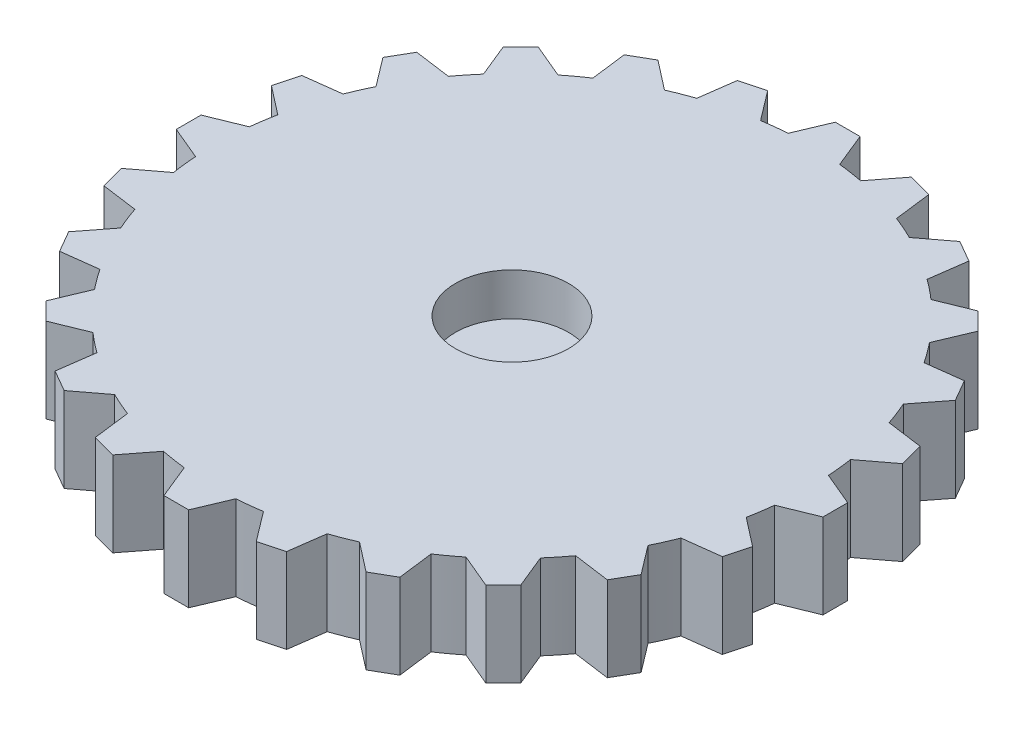
SolidWorks part; units mm, degrees
ref_plane "Front Plane" through (0, 0, 0) normal (0, 0, 1) x (1, 0, 0)
ref_plane "Top Plane" through (0, 0, 0) normal (0, 1, 0) x (1, 0, 0)
ref_plane "Right Plane" through (0, 0, 0) normal (1, 0, 0) x (0, 0, -1)
sketch "Sketch1" plane through (0, 0, 0) normal (0, 1, 0) x (1, 0, 0)
  line L111 (-0.5, 14.7462) -> (0.5, 14.7462)
  line L112 (0.5, 14.7462) -> (2, 12.5441)
  line L113 (-0.5, 14.7462) -> (-2, 12.5441)
  line L114 (6.433, 12.8885) -> (6.631, 10.2315)
  line L115 (5.567, 13.3885) -> (6.433, 12.8885)
  line L116 (5.567, 13.3885) -> (3.1669, 12.2315)
  line L117 (10.6423, 8.3132) -> (9.4853, 5.9131)
  line L118 (10.1423, 9.1792) -> (10.6423, 8.3132)
  line L119 (10.1423, 9.1792) -> (7.4853, 9.3772)
  line L120 (12, 2.2462) -> (9.798, 0.7462)
  line L121 (12, 3.2462) -> (12, 2.2462)
  line L122 (12, 3.2462) -> (9.798, 4.7462)
  line L123 (10.1423, -3.6868) -> (7.4853, -3.8849)
  line L124 (10.6423, -2.8208) -> (10.1423, -3.6868)
  line L125 (10.6423, -2.8208) -> (9.4853, -0.4208)
  line L126 (5.567, -7.8961) -> (3.1669, -6.7391)
  line L127 (6.433, -7.3961) -> (5.567, -7.8961)
  line L128 (6.433, -7.3961) -> (6.631, -4.7391)
  line L129 (-0.5, -9.2538) -> (-2, -7.0518)
  line L130 (0.5, -9.2538) -> (-0.5, -9.2538)
  line L131 (0.5, -9.2538) -> (2, -7.0518)
  line L132 (-6.433, -7.3961) -> (-6.631, -4.7391)
  line L133 (-5.567, -7.8961) -> (-6.433, -7.3961)
  line L134 (-5.567, -7.8961) -> (-3.1669, -6.7391)
  line L135 (-10.6423, -2.8208) -> (-9.4853, -0.4208)
  line L136 (-10.1423, -3.6868) -> (-10.6423, -2.8208)
  line L137 (-10.1423, -3.6868) -> (-7.4853, -3.8849)
  line L138 (-12, 3.2462) -> (-9.798, 4.7462)
  line L139 (-12, 2.2462) -> (-12, 3.2462)
  line L140 (-12, 2.2462) -> (-9.798, 0.7462)
  line L141 (-10.1423, 9.1792) -> (-7.4853, 9.3772)
  line L142 (-10.6423, 8.3132) -> (-10.1423, 9.1792)
  line L143 (-10.6423, 8.3132) -> (-9.4853, 5.9131)
  line L144 (-5.567, 13.3885) -> (-3.1669, 12.2315)
  line L145 (-6.433, 12.8885) -> (-5.567, 13.3885)
  line L146 (-6.433, 12.8885) -> (-6.631, 10.2315)
  arc A43 (-2, 12.5441) -> (-3.1669, 12.2315) centre (0, 2.7462) ccw
  arc A44 (-6.631, 10.2315) -> (-7.4853, 9.3772) centre (0, 2.7462) ccw
  arc A45 (-9.4853, 5.9131) -> (-9.798, 4.7462) centre (0, 2.7462) ccw
  arc A46 (-9.798, 0.7462) -> (-9.4853, -0.4208) centre (0, 2.7462) ccw
  arc A47 (-7.4853, -3.8849) -> (-6.631, -4.7391) centre (0, 2.7462) ccw
  arc A48 (-3.1669, -6.7391) -> (-2, -7.0518) centre (0, 2.7462) ccw
  arc A49 (2, -7.0518) -> (3.1669, -6.7391) centre (0, 2.7462) ccw
  arc A50 (6.631, -4.7391) -> (7.4853, -3.8849) centre (0, 2.7462) ccw
  arc A51 (9.4853, -0.4208) -> (9.798, 0.7462) centre (0, 2.7462) ccw
  arc A52 (9.798, 4.7462) -> (9.4853, 5.9131) centre (0, 2.7462) ccw
  arc A53 (7.4853, 9.3772) -> (6.631, 10.2315) centre (0, 2.7462) ccw
  arc A54 (3.1669, 12.2315) -> (2, 12.5441) centre (0, 2.7462) ccw
  point P6 (0, 0)
  point P8 (0, 0)
  point P9 (0, 0)
  point P12 (0, 2.7462)
  point P17 (0, 0)
  point P18 (0, 2.7462)
  point P22 (-2.5, 0.7462)
  point P63 (0, 0)
  point P68 (0, 0)
  point P69 (0, 2.7462)
  point P119 (0, 0)
  dimension "D1" = 20
  dimension "D8" = 12
sketch "Sketch2" plane through (0, 0, 0) normal (0, 1, 0) x (1, 0, 0)
  line L0 (-2, 0) -> (2, 0)
  line L1 (-23, -0.1) -> (-23, 0.1)
  line L2 (-21.1, 2) -> (-19.8997, 2)
  line L3 (-21.1, -2) -> (-19.8997, -2)
  line L4 (-20.6853, 4.6181) -> (-19.5438, 4.2472)
  line L5 (-19.4493, 8.4224) -> (-18.3078, 8.0515)
  line L6 (-21.9052, 7.0123) -> (-21.8434, 7.2025)
  line L7 (-18.2458, 10.7842) -> (-17.2748, 10.0787)
  line L8 (-15.8947, 14.0203) -> (-14.9237, 13.3148)
  line L9 (-18.6662, 13.4382) -> (-18.5486, 13.6)
  line L10 (-14.0203, 15.8947) -> (-13.3148, 14.9237)
  line L11 (-10.7842, 18.2458) -> (-10.0787, 17.2748)
  line L12 (-13.6, 18.5486) -> (-13.4382, 18.6662)
  line L13 (-8.4224, 19.4493) -> (-8.0515, 18.3078)
  line L14 (-4.6181, 20.6853) -> (-4.2472, 19.5438)
  line L15 (-7.2025, 21.8434) -> (-7.0123, 21.9052)
  line L16 (-2, 21.1) -> (-2, 19.8997)
  line L17 (2, 21.1) -> (2, 19.8997)
  line L18 (-0.1, 23) -> (0.1, 23)
  line L19 (4.6181, 20.6853) -> (4.2472, 19.5438)
  line L20 (8.4224, 19.4493) -> (8.0515, 18.3078)
  line L21 (7.0123, 21.9052) -> (7.2025, 21.8434)
  line L22 (10.7842, 18.2458) -> (10.0787, 17.2748)
  line L23 (14.0203, 15.8947) -> (13.3148, 14.9237)
  line L24 (13.4382, 18.6662) -> (13.6, 18.5486)
  line L25 (15.8947, 14.0203) -> (14.9237, 13.3148)
  line L26 (18.2458, 10.7842) -> (17.2748, 10.0787)
  line L27 (18.5486, 13.6) -> (18.6662, 13.4382)
  line L28 (19.4493, 8.4224) -> (18.3078, 8.0515)
  line L29 (20.6853, 4.6181) -> (19.5438, 4.2472)
  line L30 (21.8434, 7.2025) -> (21.9052, 7.0123)
  line L31 (21.1, 2) -> (19.8997, 2)
  line L32 (21.1, -2) -> (19.8997, -2)
  line L33 (23, 0.1) -> (23, -0.1)
  line L34 (20.6853, -4.6181) -> (19.5438, -4.2472)
  line L35 (19.4493, -8.4224) -> (18.3078, -8.0515)
  line L36 (21.9052, -7.0123) -> (21.8434, -7.2025)
  line L37 (18.2458, -10.7842) -> (17.2748, -10.0787)
  line L38 (15.8947, -14.0203) -> (14.9237, -13.3148)
  line L39 (18.6662, -13.4382) -> (18.5486, -13.6)
  line L40 (14.0203, -15.8947) -> (13.3148, -14.9237)
  line L41 (10.7842, -18.2458) -> (10.0787, -17.2748)
  line L42 (13.6, -18.5486) -> (13.4382, -18.6662)
  line L43 (8.4224, -19.4493) -> (8.0515, -18.3078)
  line L44 (4.6181, -20.6853) -> (4.2472, -19.5438)
  line L45 (7.2025, -21.8434) -> (7.0123, -21.9052)
  line L46 (2, -21.1) -> (2, -19.8997)
  line L47 (-2, -21.1) -> (-2, -19.8997)
  line L48 (0.1, -23) -> (-0.1, -23)
  line L49 (-4.6181, -20.6853) -> (-4.2472, -19.5438)
  line L50 (-8.4224, -19.4493) -> (-8.0515, -18.3078)
  line L51 (-7.0123, -21.9052) -> (-7.2025, -21.8434)
  line L52 (-10.7842, -18.2458) -> (-10.0787, -17.2748)
  line L53 (-14.0203, -15.8947) -> (-13.3148, -14.9237)
  line L54 (-13.4382, -18.6662) -> (-13.6, -18.5486)
  line L55 (-15.8947, -14.0203) -> (-14.9237, -13.3148)
  line L56 (-18.2458, -10.7842) -> (-17.2748, -10.0787)
  line L57 (-18.5486, -13.6) -> (-18.6662, -13.4382)
  line L58 (-19.4493, -8.4224) -> (-18.3078, -8.0515)
  line L59 (-20.6853, -4.6181) -> (-19.5438, -4.2472)
  line L60 (-21.8434, -7.2025) -> (-21.9052, -7.0123)
  arc A0 (-18.3078, -8.0515) -> (-17.2748, -10.0787) centre (0, 0) ccw
  arc A1 (-21.1, 2) -> (-23, 0.1) centre (-21.1, 0.1) ccw
  arc A2 (-21.1, -2) -> (-23, -0.1) centre (-21.1, -0.1) cw
  arc A3 (-20.6853, 4.6181) -> (-21.9052, 7.0123) centre (-20.0982, 6.4252) cw
  arc A4 (-19.4493, 8.4224) -> (-21.8434, 7.2025) centre (-20.0364, 6.6154) ccw
  arc A5 (-18.2458, 10.7842) -> (-18.6662, 13.4382) centre (-17.129, 12.3214) cw
  arc A6 (-15.8947, 14.0203) -> (-18.5486, 13.6) centre (-17.0115, 12.4832) ccw
  arc A7 (-14.0203, 15.8947) -> (-13.6, 18.5486) centre (-12.4832, 17.0115) cw
  arc A8 (-10.7842, 18.2458) -> (-13.4382, 18.6662) centre (-12.3214, 17.129) ccw
  arc A9 (-8.4224, 19.4493) -> (-7.2025, 21.8434) centre (-6.6154, 20.0364) cw
  arc A10 (-4.6181, 20.6853) -> (-7.0123, 21.9052) centre (-6.4252, 20.0982) ccw
  arc A11 (-2, 21.1) -> (-0.1, 23) centre (-0.1, 21.1) cw
  arc A12 (2, 21.1) -> (0.1, 23) centre (0.1, 21.1) ccw
  arc A13 (4.6181, 20.6853) -> (7.0123, 21.9052) centre (6.4252, 20.0982) cw
  arc A14 (8.4224, 19.4493) -> (7.2025, 21.8434) centre (6.6154, 20.0364) ccw
  arc A15 (10.7842, 18.2458) -> (13.4382, 18.6662) centre (12.3214, 17.129) cw
  arc A16 (14.0203, 15.8947) -> (13.6, 18.5486) centre (12.4832, 17.0115) ccw
  arc A17 (15.8947, 14.0203) -> (18.5486, 13.6) centre (17.0115, 12.4832) cw
  arc A18 (18.2458, 10.7842) -> (18.6662, 13.4382) centre (17.129, 12.3214) ccw
  arc A19 (19.4493, 8.4224) -> (21.8434, 7.2025) centre (20.0364, 6.6154) cw
  arc A20 (20.6853, 4.6181) -> (21.9052, 7.0123) centre (20.0982, 6.4252) ccw
  arc A21 (21.1, 2) -> (23, 0.1) centre (21.1, 0.1) cw
  arc A22 (21.1, -2) -> (23, -0.1) centre (21.1, -0.1) ccw
  arc A23 (20.6853, -4.6181) -> (21.9052, -7.0123) centre (20.0982, -6.4252) cw
  arc A24 (19.4493, -8.4224) -> (21.8434, -7.2025) centre (20.0364, -6.6154) ccw
  arc A25 (18.2458, -10.7842) -> (18.6662, -13.4382) centre (17.129, -12.3214) cw
  arc A26 (15.8947, -14.0203) -> (18.5486, -13.6) centre (17.0115, -12.4832) ccw
  arc A27 (14.0203, -15.8947) -> (13.6, -18.5486) centre (12.4832, -17.0115) cw
  arc A28 (10.7842, -18.2458) -> (13.4382, -18.6662) centre (12.3214, -17.129) ccw
  arc A29 (8.4224, -19.4493) -> (7.2025, -21.8434) centre (6.6154, -20.0364) cw
  arc A30 (4.6181, -20.6853) -> (7.0123, -21.9052) centre (6.4252, -20.0982) ccw
  arc A31 (2, -21.1) -> (0.1, -23) centre (0.1, -21.1) cw
  arc A32 (-2, -21.1) -> (-0.1, -23) centre (-0.1, -21.1) ccw
  arc A33 (-4.6181, -20.6853) -> (-7.0123, -21.9052) centre (-6.4252, -20.0982) cw
  arc A34 (-8.4224, -19.4493) -> (-7.2025, -21.8434) centre (-6.6154, -20.0364) ccw
  arc A35 (-10.7842, -18.2458) -> (-13.4382, -18.6662) centre (-12.3214, -17.129) cw
  arc A36 (-14.0203, -15.8947) -> (-13.6, -18.5486) centre (-12.4832, -17.0115) ccw
  arc A37 (-15.8947, -14.0203) -> (-18.5486, -13.6) centre (-17.0115, -12.4832) cw
  arc A38 (-18.2458, -10.7842) -> (-18.6662, -13.4382) centre (-17.129, -12.3214) ccw
  arc A39 (-19.4493, -8.4224) -> (-21.8434, -7.2025) centre (-20.0364, -6.6154) cw
  arc A40 (-20.6853, -4.6181) -> (-21.9052, -7.0123) centre (-20.0982, -6.4252) ccw
  arc A41 (-19.8997, -2) -> (-19.5438, -4.2472) centre (0, 0) ccw
  arc A42 (-19.5438, 4.2472) -> (-19.8997, 2) centre (0, 0) ccw
  arc A43 (-17.2748, 10.0787) -> (-18.3078, 8.0515) centre (0, 0) ccw
  arc A44 (-13.3148, 14.9237) -> (-14.9237, 13.3148) centre (0, 0) ccw
  arc A45 (-8.0515, 18.3078) -> (-10.0787, 17.2748) centre (0, 0) ccw
  arc A46 (-2, 19.8997) -> (-4.2472, 19.5438) centre (0, 0) ccw
  arc A47 (4.2472, 19.5438) -> (2, 19.8997) centre (0, 0) ccw
  arc A48 (10.0787, 17.2748) -> (8.0515, 18.3078) centre (0, 0) ccw
  arc A49 (14.9237, 13.3148) -> (13.3148, 14.9237) centre (0, 0) ccw
  arc A50 (18.3078, 8.0515) -> (17.2748, 10.0787) centre (0, 0) ccw
  arc A51 (19.8997, 2) -> (19.5438, 4.2472) centre (0, 0) ccw
  arc A52 (19.5438, -4.2472) -> (19.8997, -2) centre (0, 0) ccw
  arc A53 (17.2748, -10.0787) -> (18.3078, -8.0515) centre (0, 0) ccw
  arc A54 (13.3148, -14.9237) -> (14.9237, -13.3148) centre (0, 0) ccw
  arc A55 (8.0515, -18.3078) -> (10.0787, -17.2748) centre (0, 0) ccw
  arc A56 (2, -19.8997) -> (4.2472, -19.5438) centre (0, 0) ccw
  arc A57 (-10.0787, -17.2748) -> (-8.0515, -18.3078) centre (0, 0) ccw
  arc A58 (-4.2472, -19.5438) -> (-2, -19.8997) centre (0, 0) ccw
  arc A59 (-14.9237, -13.3148) -> (-13.3148, -14.9237) centre (0, 0) ccw
  point P6 (0, 0)
  point P10 (-23, 2)
  point P170 (0, 0)
  dimension "D1" = 40
  dimension "D4" = 1.9
  dimension "D5" = 20
sketch "Sketch3" plane through (0, 0, 0) normal (0, 1, 0) x (1, 0, 0)
  line L0 (20.6069, -4.0443) -> (20.351, -4.9991) construction
  line L1 (23.3015, -1.3115) -> (23.3015, 0.4385)
  line L2 (23.3015, 0.4385) -> (20.9515, 1.4269)
  line L3 (23.3015, -1.3115) -> (20.8737, -2.3)
  line L4 (22.621, -5.6073) -> (20.6069, -4.0443)
  line L5 (22.168, -7.2977) -> (22.621, -5.6073)
  line L6 (22.168, -7.2977) -> (19.5671, -7.6241)
  line L7 (20.3989, -11.271) -> (18.858, -9.24)
  line L8 (19.5239, -12.7866) -> (20.3989, -11.271)
  line L9 (19.5239, -12.7866) -> (16.9271, -12.4287)
  line L10 (16.7867, -16.1666) -> (15.8239, -13.8059)
  line L11 (15.5492, -17.404) -> (16.7867, -16.1666)
  line L12 (15.5492, -17.404) -> (13.1336, -16.3863)
  line L13 (12.0304, -19.9604) -> (11.7115, -17.431)
  line L14 (10.5149, -20.8354) -> (12.0304, -19.9604)
  line L15 (10.5149, -20.8354) -> (8.445, -19.2271)
  line L16 (6.4544, -22.394) -> (6.8009, -19.8682)
  line L17 (4.764, -22.8469) -> (6.4544, -22.394)
  line L18 (4.764, -22.8469) -> (3.1809, -20.7577)
  line L19 (0.4385, -23.3015) -> (1.4269, -20.9515)
  line L20 (-1.3115, -23.3015) -> (0.4385, -23.3015)
  line L21 (-1.3115, -23.3015) -> (-2.3, -20.8737)
  line L22 (-5.6073, -22.621) -> (-4.0443, -20.6069)
  line L23 (-7.2977, -22.168) -> (-5.6073, -22.621)
  line L24 (-7.2977, -22.168) -> (-7.6241, -19.5671)
  line L25 (-11.271, -20.3989) -> (-9.24, -18.858)
  line L26 (-12.7866, -19.5239) -> (-11.271, -20.3989)
  line L27 (-12.7866, -19.5239) -> (-12.4287, -16.9271)
  line L28 (-16.1666, -16.7867) -> (-13.8059, -15.8239)
  line L29 (-17.404, -15.5492) -> (-16.1666, -16.7867)
  line L30 (-17.404, -15.5492) -> (-16.3863, -13.1336)
  line L31 (-19.9604, -12.0304) -> (-17.431, -11.7115)
  line L32 (-20.8354, -10.5149) -> (-19.9604, -12.0304)
  line L33 (-20.8354, -10.5149) -> (-19.2271, -8.445)
  line L34 (-22.394, -6.4544) -> (-19.8682, -6.8009)
  line L35 (-22.8469, -4.764) -> (-22.394, -6.4544)
  line L36 (-22.8469, -4.764) -> (-20.7577, -3.1809)
  line L37 (-23.3015, -0.4385) -> (-20.9515, -1.4269)
  line L38 (-23.3015, 1.3115) -> (-23.3015, -0.4385)
  line L39 (-23.3015, 1.3115) -> (-20.8737, 2.3)
  line L40 (-22.621, 5.6073) -> (-20.6069, 4.0443)
  line L41 (-22.168, 7.2977) -> (-22.621, 5.6073)
  line L42 (-22.168, 7.2977) -> (-19.5671, 7.6241)
  line L43 (-20.3989, 11.271) -> (-18.858, 9.24)
  line L44 (-19.5239, 12.7866) -> (-20.3989, 11.271)
  line L45 (-19.5239, 12.7866) -> (-16.9271, 12.4287)
  line L46 (-16.7867, 16.1666) -> (-15.8239, 13.8059)
  line L47 (-15.5492, 17.404) -> (-16.7867, 16.1666)
  line L48 (-15.5492, 17.404) -> (-13.1336, 16.3863)
  line L49 (-12.0304, 19.9604) -> (-11.7115, 17.431)
  line L50 (-10.5149, 20.8354) -> (-12.0304, 19.9604)
  line L51 (-10.5149, 20.8354) -> (-8.445, 19.2271)
  line L52 (-6.4544, 22.394) -> (-6.8009, 19.8682)
  line L53 (-4.764, 22.8469) -> (-6.4544, 22.394)
  line L54 (-4.764, 22.8469) -> (-3.1809, 20.7577)
  line L55 (-0.4385, 23.3015) -> (-1.4269, 20.9515)
  line L56 (1.3115, 23.3015) -> (-0.4385, 23.3015)
  line L57 (1.3115, 23.3015) -> (2.3, 20.8737)
  line L58 (5.6073, 22.621) -> (4.0443, 20.6069)
  line L59 (7.2977, 22.168) -> (5.6073, 22.621)
  line L60 (7.2977, 22.168) -> (7.6241, 19.5671)
  line L61 (11.271, 20.3989) -> (9.24, 18.858)
  line L62 (12.7866, 19.5239) -> (11.271, 20.3989)
  line L63 (12.7866, 19.5239) -> (12.4287, 16.9271)
  line L64 (16.1666, 16.7867) -> (13.8059, 15.8239)
  line L65 (17.404, 15.5492) -> (16.1666, 16.7867)
  line L66 (17.404, 15.5492) -> (16.3863, 13.1336)
  line L67 (19.9604, 12.0304) -> (17.431, 11.7115)
  line L68 (20.8354, 10.5149) -> (19.9604, 12.0304)
  line L69 (20.8354, 10.5149) -> (19.2271, 8.445)
  line L70 (22.394, 6.4544) -> (19.8682, 6.8009)
  line L71 (22.8469, 4.764) -> (22.394, 6.4544)
  line L72 (22.8469, 4.764) -> (20.7577, 3.1809)
  line L73 (22.621, -5.6073) -> (20.351, -4.9991) construction
  line L74 (22.168, -7.2977) -> (19.823, -6.6694) construction
  line L75 (19.823, -6.6694) -> (19.5671, -7.6241) construction
  arc A0 (-9.24, -18.858) -> (-7.6241, -19.5671) centre (0, 0) ccw
  arc A1 (-13.8059, -15.8239) -> (-12.4287, -16.9271) centre (0, 0) ccw
  arc A2 (-17.431, -11.7115) -> (-16.3863, -13.1336) centre (0, 0) ccw
  arc A3 (-19.8682, -6.8009) -> (-19.2271, -8.445) centre (0, 0) ccw
  arc A4 (-20.9515, -1.4269) -> (-20.7577, -3.1809) centre (0, 0) ccw
  arc A5 (-20.6069, 4.0443) -> (-20.8737, 2.3) centre (0, 0) ccw
  arc A6 (-18.858, 9.24) -> (-19.5671, 7.6241) centre (0, 0) ccw
  arc A7 (-15.8239, 13.8059) -> (-16.9271, 12.4287) centre (0, 0) ccw
  arc A8 (13.8059, 15.8239) -> (12.4287, 16.9271) centre (0, 0) ccw
  arc A10 (13.8059, 15.8239) -> (12.4287, 16.9271) centre (0, 0) ccw
  arc A12 (9.24, 18.858) -> (7.6241, 19.5671) centre (0, 0) ccw
  arc A13 (13.8059, 15.8239) -> (12.4287, 16.9271) centre (0, 0) ccw
  arc A14 (17.431, 11.7115) -> (16.3863, 13.1336) centre (0, 0) ccw
  arc A15 (19.8682, 6.8009) -> (19.2271, 8.445) centre (0, 0) ccw
  arc A16 (20.9515, 1.4269) -> (20.7577, 3.1809) centre (0, 0) ccw
  arc A17 (20.6069, -4.0443) -> (20.8737, -2.3) centre (0, 0) ccw
  arc A18 (18.858, -9.24) -> (19.5671, -7.6241) centre (0, 0) ccw
  arc A19 (-4.0443, -20.6069) -> (-2.3, -20.8737) centre (0, 0) ccw
  arc A20 (1.4269, -20.9515) -> (3.1809, -20.7577) centre (0, 0) ccw
  arc A21 (6.8009, -19.8682) -> (8.445, -19.2271) centre (0, 0) ccw
  arc A22 (11.7115, -17.431) -> (13.1336, -16.3863) centre (0, 0) ccw
  arc A23 (15.8239, -13.8059) -> (16.9271, -12.4287) centre (0, 0) ccw
  arc A24 (-20.6069, 4.0443) -> (-20.8737, 2.3) centre (0, 0) ccw
  arc A25 (-20.6069, 4.0443) -> (-20.8737, 2.3) centre (0, 0) ccw
  arc A26 (-20.6069, 4.0443) -> (-20.8737, 2.3) centre (0, 0) ccw
  arc A27 (-18.858, 9.24) -> (-19.5671, 7.6241) centre (0, 0) ccw
  arc A28 (-18.858, 9.24) -> (-19.5671, 7.6241) centre (0, 0) ccw
  arc A29 (-18.858, 9.24) -> (-19.5671, 7.6241) centre (0, 0) ccw
  arc A30 (-15.8239, 13.8059) -> (-16.9271, 12.4287) centre (0, 0) ccw
  arc A31 (-15.8239, 13.8059) -> (-16.9271, 12.4287) centre (0, 0) ccw
  arc A32 (-15.8239, 13.8059) -> (-16.9271, 12.4287) centre (0, 0) ccw
  arc A33 (-11.7115, 17.431) -> (-13.1336, 16.3863) centre (0, 0) ccw
  arc A34 (-11.7115, 17.431) -> (-13.1336, 16.3863) centre (0, 0) ccw
  arc A35 (-11.7115, 17.431) -> (-13.1336, 16.3863) centre (0, 0) ccw
  arc A36 (-11.7115, 17.431) -> (-13.1336, 16.3863) centre (0, 0) ccw
  arc A37 (-6.8009, 19.8682) -> (-8.445, 19.2271) centre (0, 0) ccw
  arc A38 (-6.8009, 19.8682) -> (-8.445, 19.2271) centre (0, 0) ccw
  arc A39 (-6.8009, 19.8682) -> (-8.445, 19.2271) centre (0, 0) ccw
  arc A40 (-6.8009, 19.8682) -> (-8.445, 19.2271) centre (0, 0) ccw
  arc A41 (-1.4269, 20.9515) -> (-3.1809, 20.7577) centre (0, 0) ccw
  arc A42 (-1.4269, 20.9515) -> (-3.1809, 20.7577) centre (0, 0) ccw
  arc A43 (-1.4269, 20.9515) -> (-3.1809, 20.7577) centre (0, 0) ccw
  arc A44 (-1.4269, 20.9515) -> (-3.1809, 20.7577) centre (0, 0) ccw
  arc A45 (4.0443, 20.6069) -> (2.3, 20.8737) centre (0, 0) ccw
  arc A46 (4.0443, 20.6069) -> (2.3, 20.8737) centre (0, 0) ccw
  arc A47 (4.0443, 20.6069) -> (2.3, 20.8737) centre (0, 0) ccw
  arc A48 (4.0443, 20.6069) -> (2.3, 20.8737) centre (0, 0) ccw
  arc A49 (9.24, 18.858) -> (7.6241, 19.5671) centre (0, 0) ccw
  arc A50 (9.24, 18.858) -> (7.6241, 19.5671) centre (0, 0) ccw
  arc A51 (9.24, 18.858) -> (7.6241, 19.5671) centre (0, 0) ccw
  arc A52 (13.8059, 15.8239) -> (12.4287, 16.9271) centre (0, 0) ccw
  arc A53 (17.431, 11.7115) -> (16.3863, 13.1336) centre (0, 0) ccw
  arc A54 (19.8682, 6.8009) -> (19.2271, 8.445) centre (0, 0) ccw
  arc A55 (20.9515, 1.4269) -> (20.7577, 3.1809) centre (0, 0) ccw
  arc A56 (20.9515, 1.4269) -> (20.7577, 3.1809) centre (0, 0) ccw
  arc A57 (20.9515, 1.4269) -> (20.7577, 3.1809) centre (0, 0) ccw
  arc A58 (20.6069, -4.0443) -> (20.8737, -2.3) centre (0, 0) ccw
  arc A59 (20.6069, -4.0443) -> (20.8737, -2.3) centre (0, 0) ccw
  arc A60 (20.6069, -4.0443) -> (20.8737, -2.3) centre (0, 0) ccw
  arc A61 (18.858, -9.24) -> (19.5671, -7.6241) centre (0, 0) ccw
  arc A62 (18.858, -9.24) -> (19.5671, -7.6241) centre (0, 0) ccw
  arc A63 (18.858, -9.24) -> (19.5671, -7.6241) centre (0, 0) ccw
  arc A64 (15.8239, -13.8059) -> (16.9271, -12.4287) centre (0, 0) ccw
  arc A65 (15.8239, -13.8059) -> (16.9271, -12.4287) centre (0, 0) ccw
  arc A66 (15.8239, -13.8059) -> (16.9271, -12.4287) centre (0, 0) ccw
  arc A67 (11.7115, -17.431) -> (13.1336, -16.3863) centre (0, 0) ccw
  arc A68 (11.7115, -17.431) -> (13.1336, -16.3863) centre (0, 0) ccw
  arc A69 (11.7115, -17.431) -> (13.1336, -16.3863) centre (0, 0) ccw
  arc A70 (6.8009, -19.8682) -> (8.445, -19.2271) centre (0, 0) ccw
  arc A71 (6.8009, -19.8682) -> (8.445, -19.2271) centre (0, 0) ccw
  arc A72 (6.8009, -19.8682) -> (8.445, -19.2271) centre (0, 0) ccw
  arc A73 (1.4269, -20.9515) -> (3.1809, -20.7577) centre (0, 0) ccw
  arc A74 (1.4269, -20.9515) -> (3.1809, -20.7577) centre (0, 0) ccw
  arc A75 (1.4269, -20.9515) -> (3.1809, -20.7577) centre (0, 0) ccw
  arc A76 (-4.0443, -20.6069) -> (-2.3, -20.8737) centre (0, 0) ccw
  arc A77 (-4.0443, -20.6069) -> (-2.3, -20.8737) centre (0, 0) ccw
  arc A78 (-4.0443, -20.6069) -> (-2.3, -20.8737) centre (0, 0) ccw
  arc A79 (-9.24, -18.858) -> (-7.6241, -19.5671) centre (0, 0) ccw
  arc A80 (-9.24, -18.858) -> (-7.6241, -19.5671) centre (0, 0) ccw
  arc A81 (-9.24, -18.858) -> (-7.6241, -19.5671) centre (0, 0) ccw
  arc A82 (-13.8059, -15.8239) -> (-12.4287, -16.9271) centre (0, 0) ccw
  arc A83 (-13.8059, -15.8239) -> (-12.4287, -16.9271) centre (0, 0) ccw
  arc A84 (-13.8059, -15.8239) -> (-12.4287, -16.9271) centre (0, 0) ccw
  arc A85 (-17.431, -11.7115) -> (-16.3863, -13.1336) centre (0, 0) ccw
  arc A86 (-17.431, -11.7115) -> (-16.3863, -13.1336) centre (0, 0) ccw
  arc A87 (-17.431, -11.7115) -> (-16.3863, -13.1336) centre (0, 0) ccw
  arc A88 (-19.8682, -6.8009) -> (-19.2271, -8.445) centre (0, 0) ccw
  arc A89 (-19.8682, -6.8009) -> (-19.2271, -8.445) centre (0, 0) ccw
  arc A90 (-19.8682, -6.8009) -> (-19.2271, -8.445) centre (0, 0) ccw
  arc A91 (-20.9515, -1.4269) -> (-20.7577, -3.1809) centre (0, 0) ccw
  arc A92 (-20.9515, -1.4269) -> (-20.7577, -3.1809) centre (0, 0) ccw
  arc A93 (-20.9515, -1.4269) -> (-20.7577, -3.1809) centre (0, 0) ccw
  point P6 (0, 0)
  point P7 (0, -12.952)
  point P8 (-6.2727, 0)
  point P9 (11.4668, 0)
  point P10 (0, 0)
  point P108 (0, 0)
  dimension "D1" = 42
  dimension "D4" = 24
  dimension "1." = 1.75
  dimension "2.5" = 2.35
extrude "Boss-Extrude5" add sketch "Sketch3" along normal blind 6 separate body contours A10 A24 A15 A14 A8 A7 A6 A5 A12 | A10 A4 A3 A2 A1 A0 region at (0, 0, 0)
extrude "Boss-Extrude6" add sketch "Sketch1" along normal blind 3 separate body
sketch "Sketch4" plane through (0, 6, 0) normal (0, 1, 0) x (1, 0, 0)
  circle A0 centre (0, 0) radius 4
  dimension "D1" = 8
extrude "Cut-Extrude1" cut sketch "Sketch4" against normal blind 10
sketch "Sketch5" plane through (0, 6, 0) normal (0, 1, 0) x (1, 0, 0)
  line L0 (-14.4568, -4) -> (14.4568, -4) construction
  circle A0 centre (-14.4568, -4) radius 1.5
  circle A1 centre (0, 0) radius 4 construction
  circle A2 centre (14.4568, -4) radius 1.5
  dimension "D1" = 3
  dimension "D2" = 15
  dimension "D3" = 3
  dimension "D4" = 15
extrude "Cut-Extrude2" [suppressed] cut sketch "Sketch5" against normal through all
